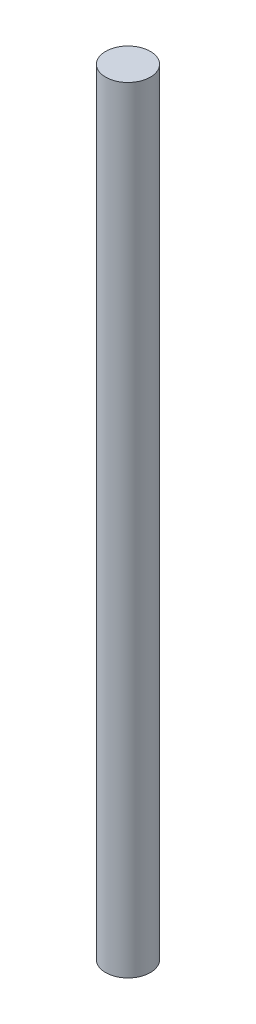
SolidWorks part; units mm, degrees
ref_plane "Front Plane" through (0, 0, 0) normal (0, 0, 1) x (1, 0, 0)
ref_plane "Top Plane" through (0, 0, 0) normal (0, 1, 0) x (1, 0, 0)
ref_plane "Right Plane" through (0, 0, 0) normal (1, 0, 0) x (0, 0, -1)
ref_axis "Axis1" through (-33.0333, 0, 0) along (1, 0, 0)
ref_axis "Axis2" through (0, 24.5224, 0) along (0, -1, 0)
ref_axis "Axis3" through (0, 0, -52.9538) along (0, 0, 1)
sketch "Sketch2" plane through (0, 0, 0) normal (0, 0, 1) x (1, 0, 0)
  line L8 (0, 60.65) -> (0, -60.65)
  line L20 (0, -60.65) -> (3.95, -60.65)
  line L21 (3.95, -60.65) -> (3.95, 84.55)
  line L23 (0, 60.65) -> (0, 84.55)
  line L24 (0, 84.55) -> (3.95, 84.55)
  point P2 (0, 0)
  dimension "D2" = 3.95
  dimension "D1" = 121.3
  dimension "D3" = 23.9
revolve "Revolve1" add sketch "Sketch2" angle 360 about axis through (0, 24.5224, 0) along (0, -1, 0) region at (1.975, 11.95, 0)
scale "Scale1" scale about origin uniform scaling no x scale factor 1.07 y scale factor 1.01 z scale factor 1.07
